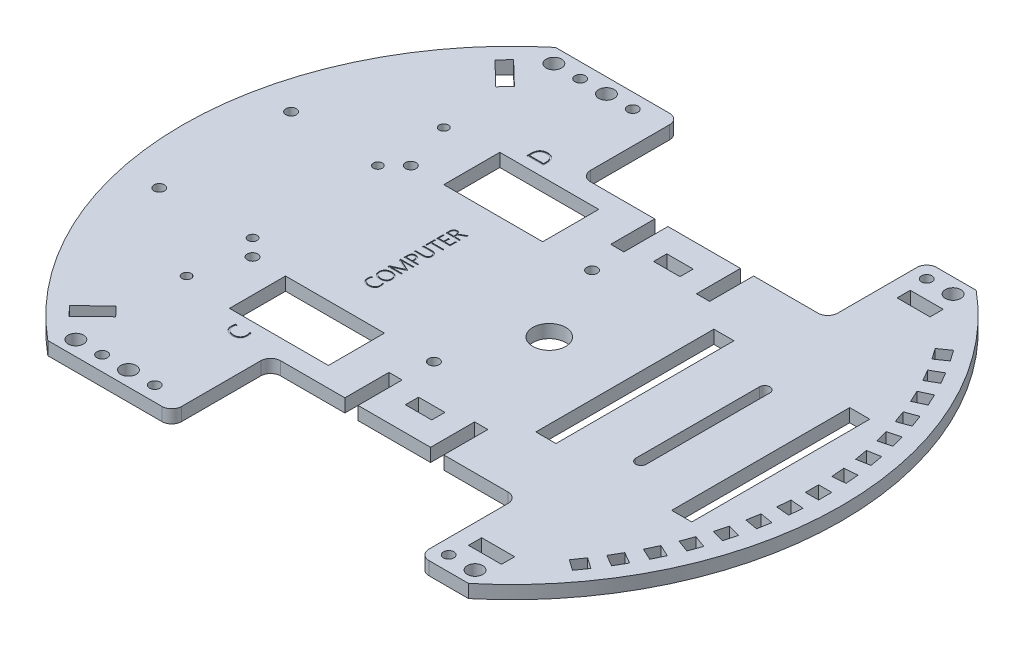
SolidWorks part; units mm, degrees
material "Oak"
ref_plane "Front Plane" through (0, 0, 0) normal (0, 0, 1) x (1, 0, 0)
ref_plane "Top Plane" through (0, 0, 0) normal (0, 1, 0) x (1, 0, 0)
ref_plane "Right Plane" through (0, 0, 0) normal (1, 0, 0) x (0, 0, -1)
sketch "Sketch1" plane through (0, 0, 0) normal (0, 1, 0) x (1, 0, 0)
  line L0 (-63.8044, 77) -> (63.8044, 77)
  line L1 (-63.8044, -77) -> (63.8044, -77)
  circle A0 centre (0, 0) radius 100
  dimension "D1" = 200
  dimension "D2" = 154
extrude "Basis" add sketch "Sketch1" along normal blind 4 contours L1 A0 L0 region at (0, 0, 0)
sketch "Sketch2" plane through (0, 4, 0) normal (0, 1, 0) x (1, 0, 0)
  line L0 (90.817, -6.1912) -> (94.8018, -6.5398)
  line L1 (91, -2) -> (95, -2)
  line L2 (91, -2) -> (91, 2)
  line L3 (91, 2) -> (95, 2)
  line L4 (95, -2) -> (95, 2)
  line L5 (90.4684, -10.176) -> (90.817, -6.1912)
  line L6 (90.4684, -10.176) -> (94.4532, -10.5246)
  line L7 (94.4532, -10.5246) -> (94.8018, -6.5398)
  line L8 (89.9208, -14.3352) -> (93.86, -15.0298)
  line L9 (89.2262, -18.2745) -> (89.9208, -14.3352)
  line L10 (89.2262, -18.2745) -> (93.1654, -18.9691)
  line L11 (93.1654, -18.9691) -> (93.86, -15.0298)
  line L12 (88.3182, -22.3702) -> (92.1819, -23.4055)
  line L13 (87.2829, -26.2339) -> (88.3182, -22.3702)
  line L14 (87.2829, -26.2339) -> (91.1466, -27.2692)
  line L15 (91.1466, -27.2692) -> (92.1819, -23.4055)
  line L16 (86.0214, -30.2349) -> (89.7802, -31.603)
  line L17 (84.6533, -33.9937) -> (86.0214, -30.2349)
  line L18 (84.6533, -33.9937) -> (88.4121, -35.3618)
  line L19 (88.4121, -35.3618) -> (89.7802, -31.603)
  line L20 (83.0479, -37.8695) -> (86.6731, -39.56)
  line L21 (81.3574, -41.4948) -> (83.0479, -37.8695)
  line L22 (81.3574, -41.4948) -> (84.9827, -43.1852)
  line L23 (84.9827, -43.1852) -> (86.6731, -39.56)
  line L24 (79.4203, -45.2159) -> (82.8844, -47.2159)
  line L25 (77.4203, -48.68) -> (79.4203, -45.2159)
  line L26 (77.4203, -48.68) -> (80.8844, -50.68)
  line L27 (80.8844, -50.68) -> (82.8844, -47.2159)
  line L28 (75.1663, -52.2182) -> (78.4429, -54.5125)
  line L29 (72.872, -55.4948) -> (75.1663, -52.2182)
  line L30 (72.872, -55.4948) -> (76.1486, -57.7891)
  line L31 (76.1486, -57.7891) -> (78.4429, -54.5125)
  line L32 (-2.896, 0) -> (91, -2) construction
  line L33 (-2.896, 0) -> (90.4684, -10.176) construction
  line L34 (90.4684, 10.176) -> (94.4532, 10.5246)
  line L35 (90.817, 6.1912) -> (90.4684, 10.176)
  line L36 (90.817, 6.1912) -> (94.8018, 6.5398)
  line L37 (94.8018, 6.5398) -> (94.4532, 10.5246)
  line L38 (89.2262, 18.2745) -> (93.1654, 18.9691)
  line L39 (89.9208, 14.3352) -> (89.2262, 18.2745)
  line L40 (89.9208, 14.3352) -> (93.86, 15.0298)
  line L41 (93.86, 15.0298) -> (93.1654, 18.9691)
  line L42 (87.2829, 26.2339) -> (91.1466, 27.2692)
  line L43 (88.3182, 22.3702) -> (87.2829, 26.2339)
  line L44 (88.3182, 22.3702) -> (92.1819, 23.4055)
  line L45 (92.1819, 23.4055) -> (91.1466, 27.2692)
  line L46 (84.6533, 33.9937) -> (88.4121, 35.3618)
  line L47 (86.0214, 30.2349) -> (84.6533, 33.9937)
  line L48 (86.0214, 30.2349) -> (89.7802, 31.603)
  line L49 (89.7802, 31.603) -> (88.4121, 35.3618)
  line L50 (81.3574, 41.4948) -> (84.9827, 43.1852)
  line L51 (83.0479, 37.8695) -> (81.3574, 41.4948)
  line L52 (83.0479, 37.8695) -> (86.6731, 39.56)
  line L53 (86.6731, 39.56) -> (84.9827, 43.1852)
  line L54 (77.4203, 48.68) -> (80.8844, 50.68)
  line L55 (79.4203, 45.2159) -> (77.4203, 48.68)
  line L56 (79.4203, 45.2159) -> (82.8844, 47.2159)
  line L57 (82.8844, 47.2159) -> (80.8844, 50.68)
  line L58 (72.872, 55.4948) -> (76.1486, 57.7891)
  line L59 (75.1663, 52.2182) -> (72.872, 55.4948)
  line L60 (75.1663, 52.2182) -> (78.4429, 54.5125)
  line L61 (78.4429, 54.5125) -> (76.1486, 57.7891)
  line L62 (-2.896, 0) -> (91, -2) construction
  line L63 (-2.896, 0) -> (90.817, 6.1912) construction
  line L64 (-2.896, 0) -> (-129.2077, 0) construction
  arc A2 (60.6142, -73.15) -> (60.6142, 73.15) centre (0, 0) ccw
  arc A3 (60.6142, -73.15) -> (60.6142, 73.15) centre (0, 0) ccw construction
  point P4 (95, 0)
  point P5 (95, 0)
  dimension "D4" = 5
  dimension "D6" = 5
  dimension "D2" = 4
  dimension "D3" = 8
extrude "Modu bracket " cut sketch "Sketch2" against normal up to surface (4 mm away) up to face at (0, 0, 0)
sketch "Sketch3" plane through (0, 4, 0) normal (0, 1, 0) x (1, 0, 0)
  line L0 (-63.8044, -77) -> (63.8044, -77) construction
  line L1 (-26.1956, -77) -> (48.8044, -77)
  line L2 (-26.1956, -77) -> (-26.1956, -47)
  line L3 (-26.1956, -47) -> (48.8044, -47)
  line L4 (48.8044, -77) -> (48.8044, -47)
  line L5 (-63.8044, 77) -> (63.8044, 77) construction
  line L6 (-26.1956, 77) -> (48.8044, 77)
  line L7 (-26.1956, 77) -> (-26.1956, 47)
  line L8 (-26.1956, 47) -> (48.8044, 47)
  line L9 (48.8044, 77) -> (48.8044, 47)
  line L10 (11.3044, -47) -> (11.3044, 47) construction
  line L11 (27.8397, 0) -> (-25.9783, 0) construction
  line L12 (7.8044, -28.15) -> (14.8044, -28.15) construction
  line L13 (7.8044, -28.15) -> (7.8044, -12.65) construction
  line L14 (7.8044, -12.65) -> (14.8044, -12.65) construction
  line L15 (14.8044, -28.15) -> (14.8044, -12.65) construction
  line L16 (7.8044, -28.15) -> (14.8044, -12.65) construction
  line L17 (7.8044, -12.65) -> (14.8044, -28.15) construction
  line L18 (0.8044, -24.15) -> (21.8044, -24.15) construction
  line L19 (0.8044, -24.15) -> (0.8044, -18.65) construction
  line L20 (0.8044, -18.65) -> (21.8044, -18.65) construction
  line L21 (21.8044, -24.15) -> (21.8044, -18.65) construction
  line L22 (0.8044, -24.15) -> (21.8044, -18.65) construction
  line L23 (0.8044, -18.65) -> (21.8044, -24.15) construction
  line L24 (0.8044, 18.65) -> (21.8044, 24.15) construction
  line L25 (0.8044, 24.15) -> (21.8044, 18.65) construction
  line L26 (7.8044, 12.65) -> (14.8044, 28.15) construction
  line L27 (7.8044, 28.15) -> (14.8044, 12.65) construction
  line L28 (21.8044, 24.15) -> (21.8044, 18.65) construction
  line L29 (0.8044, 18.65) -> (21.8044, 18.65) construction
  line L30 (0.8044, 24.15) -> (0.8044, 18.65) construction
  line L31 (0.8044, 24.15) -> (21.8044, 24.15) construction
  line L32 (14.8044, 28.15) -> (14.8044, 12.65) construction
  line L33 (7.8044, 12.65) -> (14.8044, 12.65) construction
  line L34 (7.8044, 28.15) -> (7.8044, 12.65) construction
  line L35 (7.8044, 28.15) -> (14.8044, 28.15) construction
  line L36 (7.3044, 35.65) -> (15.3044, 39.65) construction
  line L37 (7.3044, -39.65) -> (15.3044, -39.65)
  line L38 (7.3044, -39.65) -> (7.3044, -35.65)
  line L39 (7.3044, -35.65) -> (15.3044, -35.65)
  line L40 (15.3044, -39.65) -> (15.3044, -35.65)
  line L41 (7.3044, -39.65) -> (15.3044, -35.65) construction
  line L42 (7.3044, -35.65) -> (15.3044, -39.65) construction
  line L43 (7.3044, 39.65) -> (15.3044, 35.65) construction
  line L44 (15.3044, 39.65) -> (15.3044, 35.65)
  line L45 (7.3044, 35.65) -> (15.3044, 35.65)
  line L46 (7.3044, 39.65) -> (7.3044, 35.65)
  line L47 (7.3044, 39.65) -> (15.3044, 39.65)
  circle A0 centre (11.3044, 0) radius 5
  circle A1 centre (11.3044, -10.15) radius 1.6 construction
  circle A3 centre (11.3044, 10.15) radius 1.6 construction
  point P21 (11.3044, -20.4)
  point P26 (11.3044, -21.4)
  point P42 (11.3044, 21.4)
  point P43 (11.3044, 20.4)
  point P44 (11.3044, -37.65)
  point P53 (11.3044, 37.65)
  point P54 (11.3044, -28.15)
  dimension "D4" = 10
  dimension "D5" = 3.2
  dimension "D1" = 30
  dimension "D2" = 75
  dimension "D3" = 15
  dimension "D6" = 7
  dimension "D7" = 5.5
  dimension "D8" = 4
  dimension "D9" = 21
  dimension "D10" = 6
  dimension "D11" = 2.5
  dimension "D12" = 8
  dimension "D13" = 4
  dimension "D14" = 7.35
  dimension "D15" = 7.5
extrude "Cut-Extrude2" cut sketch "Sketch3" against normal through all contours L1 L4 L3 L2 | L13 L20 L15 L14 | L20 L13 L18 L15 | L20 L19 L18 L13 | L18 L13 L12 L15 | L18 L21 L20 L15 | A0 | A3 | A1 | L29 L34 L33 L32 | L31 L34 L29 L32 | L34 L31 L30 L29 | L35 L34 L31 L32 | L31 L32 L29 L28 | L47 L46 L45 L44 | L9 L6 L7 L8 | L39 L40 L37 L38 region at (11.3044, 4, 62) region at (11.3044, 4, -62) region at (11.3044, 4, -37.65) region at (11.3044, 4, 0)
sketch "Sketch4" plane through (0, 4, 0) normal (0, 1, 0) x (1, 0, 0)
  line L0 (57.8821, -18.75) -> (57.8821, 18.75) construction
  line L1 (56.2821, -18.75) -> (56.2821, 18.75)
  line L2 (59.4821, -18.75) -> (59.4821, 18.75)
  line L4 (75.4321, -27) -> (81.5321, -27)
  line L5 (75.4321, -27) -> (75.4321, 27)
  line L6 (75.4321, 27) -> (81.5321, 27)
  line L7 (81.5321, -27) -> (81.5321, 27)
  line L8 (57.8821, -38.7193) -> (57.8821, 52.9351) construction
  line L9 (40.3321, 27) -> (34.2321, 27)
  line L10 (34.2321, -27) -> (34.2321, 27)
  line L11 (40.3321, -27) -> (34.2321, -27)
  line L12 (40.3321, -27) -> (40.3321, 27)
  arc A0 (56.2821, -18.75) -> (59.4821, -18.75) centre (57.8821, -18.75) ccw
  arc A1 (59.4821, 18.75) -> (56.2821, 18.75) centre (57.8821, 18.75) ccw
  point P2 (57.8821, 0)
  point P12 (75.4321, 0)
  dimension "D1" = 37.5
  dimension "D2" = 3.2
  dimension "D3" = 54
  dimension "D4" = 15.95
  dimension "D5" = 6.1
extrude "Cut-Extrude3" cut sketch "Sketch4" against normal up to surface (4 mm away) up to face at (11.3044, 0, 37.65)
sketch "Sketch5" plane through (0, 4, 0) normal (0, 1, 0) x (1, 0, 0)
  line L0 (11.3044, -47) -> (11.3044, 47) construction
  line L1 (-3.6956, -47.64) -> (0.3044, -47.64)
  line L2 (-3.6956, -47.64) -> (-3.6956, -33.64)
  line L3 (-3.6956, -33.64) -> (0.3044, -33.64)
  line L4 (0.3044, -47.64) -> (0.3044, -33.64)
  line L5 (-3.6956, 33.64) -> (0.3044, 33.64)
  line L6 (-3.6956, 33.64) -> (-3.6956, 47.64)
  line L7 (-3.6956, 47.64) -> (0.3044, 47.64)
  line L8 (0.3044, 33.64) -> (0.3044, 47.64)
  line L9 (-26.1956, -47) -> (48.8044, -47) construction
  line L10 (-26.1956, 47) -> (48.8044, 47) construction
  line L11 (26.3044, 47.64) -> (22.3044, 47.64)
  line L12 (22.3044, 33.64) -> (22.3044, 47.64)
  line L13 (26.3044, 33.64) -> (22.3044, 33.64)
  line L14 (26.3044, 33.64) -> (26.3044, 47.64)
  line L15 (26.3044, -33.64) -> (22.3044, -33.64)
  line L16 (22.3044, -47.64) -> (22.3044, -33.64)
  line L17 (26.3044, -47.64) -> (22.3044, -47.64)
  line L18 (26.3044, -47.64) -> (26.3044, -33.64)
  dimension "D2" = 14
  dimension "D1" = 4
  dimension "D4" = 22
  dimension "D3" = 13.36
  dimension "D5" = 67.28
extrude "Cut-Extrude4" cut sketch "Sketch5" against normal up to surface (4 mm away) up to face at (37.2821, 0, 0)
sketch "Sketch6" plane through (0, 4, 0) normal (0, 1, 0) x (1, 0, 0)
  line L0 (-95, 0) -> (-54.152, 0) construction
  line L5 (-62.5181, 57.5927) -> (-59.7394, 60.47)
  line L6 (-69.7115, 64.5392) -> (-62.5181, 57.5927)
  line L7 (-66.9328, 67.4166) -> (-69.7115, 64.5392)
  line L8 (-59.7394, 60.47) -> (-66.9328, 67.4166)
  line L9 (-59.7394, -60.47) -> (-62.5181, -57.5927)
  line L10 (53.8044, -67) -> (63.8044, -67)
  line L11 (53.8044, -67) -> (53.8044, -63)
  line L12 (53.8044, -63) -> (63.8044, -63)
  line L13 (63.8044, -67) -> (63.8044, -63)
  line L14 (48.8044, -77) -> (48.8044, -47) construction
  line L15 (48.8044, -77) -> (63.8044, -77) construction
  line L16 (53.8044, 63) -> (63.8044, 63)
  line L17 (63.8044, 67) -> (63.8044, 63)
  line L18 (53.8044, 67) -> (63.8044, 67)
  line L19 (53.8044, 67) -> (53.8044, 63)
  line L20 (-66.9328, -67.4166) -> (-59.7394, -60.47)
  line L21 (-69.7115, -64.5392) -> (-66.9328, -67.4166)
  line L22 (-62.5181, -57.5927) -> (-69.7115, -64.5392)
  circle A0 centre (0, 0) radius 95 construction
  arc A1 (-77.7809, -54.5448) -> (-77.7809, 54.5448) centre (0, 0) cw construction
  arc A2 (-63.8044, 77) -> (-63.8044, -77) centre (0, 0) ccw construction
  dimension "D5" = 5
  dimension "D1" = 10
  dimension "D2" = 4
  dimension "D3" = 5
  dimension "D4" = 10
  dimension "D6" = 44
  dimension "D8" = 10
  dimension "D9" = 4
  dimension "D10" = 44
extrude "Cut-Extrude5" cut sketch "Sketch6" against normal up to surface (4 mm away) up to face at (9.6895, 0, 0)
sketch "Sketch9" plane through (0, 4, 0) normal (0, 1, 0) x (1, 0, 0)
  line L1 (-54.6956, -24) -> (0.3044, -24) construction
  line L2 (-54.6956, -24) -> (-54.6956, 24) construction
  line L3 (-54.6956, 24) -> (0.3044, 24) construction
  line L4 (0.3044, -24) -> (0.3044, 24) construction
  line L5 (-54.6956, -24) -> (0.3044, 24) construction
  line L6 (-54.6956, 24) -> (0.3044, -24) construction
  line L7 (-59.6956, 42.5) -> (-3.6956, 42.5) construction
  line L8 (-59.6956, 42.5) -> (-59.6956, -42.5) construction
  line L9 (-59.6956, -42.5) -> (-3.6956, -42.5) construction
  line L10 (-3.6956, 42.5) -> (-3.6956, -42.5) construction
  line L11 (-59.6956, -19) -> (-3.6956, -19) construction
  line L12 (-59.6956, -19) -> (-59.6956, 39) construction
  line L13 (-59.6956, 39) -> (-3.6956, 39) construction
  line L14 (-3.6956, -19) -> (-3.6956, 39) construction
  line L16 (-3.6956, 47) -> (-3.6956, 33.64) construction
  line L18 (-59.6956, -39) -> (-3.6956, -39) construction
  line L19 (-59.6956, -39) -> (-59.6956, 19) construction
  line L20 (-59.6956, 19) -> (-3.6956, 19) construction
  line L21 (-3.6956, -39) -> (-3.6956, 19) construction
  circle A0 centre (-54.6956, -24) radius 1.6
  circle A1 centre (-54.6956, 24) radius 1.6
  circle A2 centre (0.3044, 24) radius 1.6
  circle A3 centre (0.3044, -24) radius 1.6
  circle A4 centre (-59.6956, 39) radius 1.375
  circle A6 centre (-59.6956, -19) radius 1.375
  circle A7 centre (-59.6956, 19) radius 1.375
  circle A8 centre (-59.6956, -39) radius 1.375
  point P0 (-27.1956, 0)
  point P23 (-3.6956, 0)
  dimension "D1" = 3.2
  dimension "D9" = 2.75
  dimension "D2" = 48
  dimension "D3" = 55
  dimension "D4" = 11
  dimension "D5" = 85
  dimension "D6" = 56
  dimension "D7" = 58
  dimension "D8" = 3.5
  dimension "D10" = 3.5
  dimension "D11" = 58
extrude "Cut-Extrude7" cut sketch "Sketch9" against normal up to surface (4 mm away) up to face at (-64.7254, 0, -62.5046)
sketch "Sketch10" plane through (0, 4, 0) normal (0, 1, 0) x (1, 0, 0)
  line L0 (-100, 0) -> (100, 0) construction
  line L15 (-44.6956, 41) -> (-14.6956, 41)
  line L16 (-44.6956, -24) -> (-14.6956, -24)
  line L17 (-44.6956, -24) -> (-44.6956, -41)
  line L18 (-44.6956, -41) -> (-14.6956, -41)
  line L19 (-14.6956, -24) -> (-14.6956, -41)
  line L20 (-14.6956, 24) -> (-14.6956, 41)
  line L21 (-44.6956, 24) -> (-14.6956, 24)
  line L22 (-44.6956, 24) -> (-44.6956, 41)
  arc A8 (-63.8044, 77) -> (-63.8044, -77) centre (0, 0) ccw construction
  arc A9 (63.8044, -77) -> (63.8044, 77) centre (0, 0) ccw construction
  dimension "D1" = 17
  dimension "D2" = 30
  dimension "D3" = 10
extrude "Cut-Extrude8" cut sketch "Sketch10" against normal up to surface (4 mm away) up to face at (-59.6956, 0, -37.625)
sketch "Sketch11" plane through (0, 4, 0) normal (0, 1, 0) x (1, 0, 0)
  line L0 (-87, -20) -> (-87, 20) construction
  arc A0 (-63.8044, 77) -> (-63.8044, -77) centre (0, 0) ccw construction
  circle A1 centre (-87, -20) radius 1.6
  circle A2 centre (-87, 20) radius 1.6
  point P6 (-87, 0)
  dimension "D2" = 3.2
  dimension "D1" = 40
  dimension "D3" = 87
extrude "Cut-Extrude9" cut sketch "Sketch11" against normal up to surface (4 mm away) up to face at (-29.6956, 0, 32.5)
sketch "Sketch19" plane through (0, 4, 0) normal (0, 1, 0) x (1, 0, 0)
  line L1 (-44.6956, 41) -> (-44.6956, 24) construction
  line L6 (-14.6956, 41) -> (-44.6956, 41) construction
  line L8 (-44.6956, -41) -> (-14.6956, -41) construction
  line L12 (-27.6201, 20) -> (-27.6201, -20) construction
  line L13 (-34.6956, 51) -> (-34.6956, 41) construction
  line L14 (-34.6956, -41) -> (-34.6956, -51) construction
  text T0 "COMPUTER" font "Yu Gothic UI Semilight" height 4
  text T1 "D" font "Yu Gothic UI Semilight" height 5
  text T2 "C" font "Yu Gothic UI Semilight" height 5
  point P3 (-27.6201, 0)
  dimension "D1" = 40
  dimension "D2" = 10
  dimension "D3" = 10
  dimension "D4" = 10
extrude "Cut-Extrude15" cut sketch "Sketch19" against normal blind 0.2
sketch "Sketch21" plane through (0, 4, 0) normal (0, 1, 0) x (1, 0, 0)
  line L0 (-63.8044, -77) -> (-26.1956, -77) construction
  line L1 (48.8044, -77) -> (48.8044, -47) construction
  line L2 (-100, 0) -> (100, 0) construction
  circle A0 centre (-59.8044, -72.5) radius 2.35
  circle A1 centre (-51.8244, -72.5) radius 2.35 construction
  circle A2 centre (-43.8444, -72.5) radius 2.35
  circle A3 centre (-35.8644, -72.5) radius 2.35 construction
  circle A4 centre (53.3044, -72.5) radius 2.35 construction
  circle A5 centre (61.2844, -72.5) radius 2.35
  arc A7 (63.8044, -77) -> (63.8044, 77) centre (0, 0) ccw construction
  circle A8 centre (61.2844, 72.5) radius 2.35
  circle A9 centre (53.3044, 72.5) radius 2.35 construction
  circle A10 centre (-35.8644, 72.5) radius 2.35 construction
  circle A11 centre (-43.8444, 72.5) radius 2.35
  circle A12 centre (-51.8244, 72.5) radius 2.35 construction
  circle A13 centre (-59.8044, 72.5) radius 2.35
  circle A14 centre (-51.8244, -72.5) radius 1.6
  circle A15 centre (-35.8644, -72.5) radius 1.6
  circle A16 centre (53.3044, -72.5) radius 1.6
  circle A17 centre (53.3044, 72.5) radius 1.6
  circle A18 centre (-35.8644, 72.5) radius 1.6
  circle A19 centre (-51.8244, 72.5) radius 1.6
  dimension "D1" = 4.7
  dimension "D8" = 3.2
  dimension "D2" = 4.5
  dimension "D3" = 4
  dimension "D5" = 7.98
  dimension "D6" = 4.5
  dimension "D7" = 7.98
  dimension "D4" = 4
extrude "Cut-Extrude16" cut sketch "Sketch21" against normal up to surface (4 mm away) up to face at (-87, 0, 21.6)
ref_plane "Plane1" through (0, 16, 0) normal (0, 1, 0) x (1, 0, 0)
fillet "Fillet1" radius 3 8 edges at (48.8044, 2, 77) (48.8044, 2, 47) (-26.1956, 2, 77) (-26.1956, 2, 47) (48.8044, 2, -47) (48.8044, 2, -77) (-26.1956, 2, -77) (-26.1956, 2, -47)
equation "\"WT\"=4"
equation "\"M3_hole\" = 3.2"
equation "\"D5@Sketch3\"=\"M3_hole\""
equation "\"D2@Sketch4\"=\"M3_hole\""
equation "\"D1@Sketch5\"= \"WT\""
equation "\"D2@Sketch2\"=\"WT\""
equation "\"WIG_OPENING\"=10"
equation "\"D1@Sketch9\"=\"M3_hole\""
equation "\"D2@Sketch11\"=\"M3_hole\""
equation "\"D8@Sketch21\"=\"M3_hole\""
